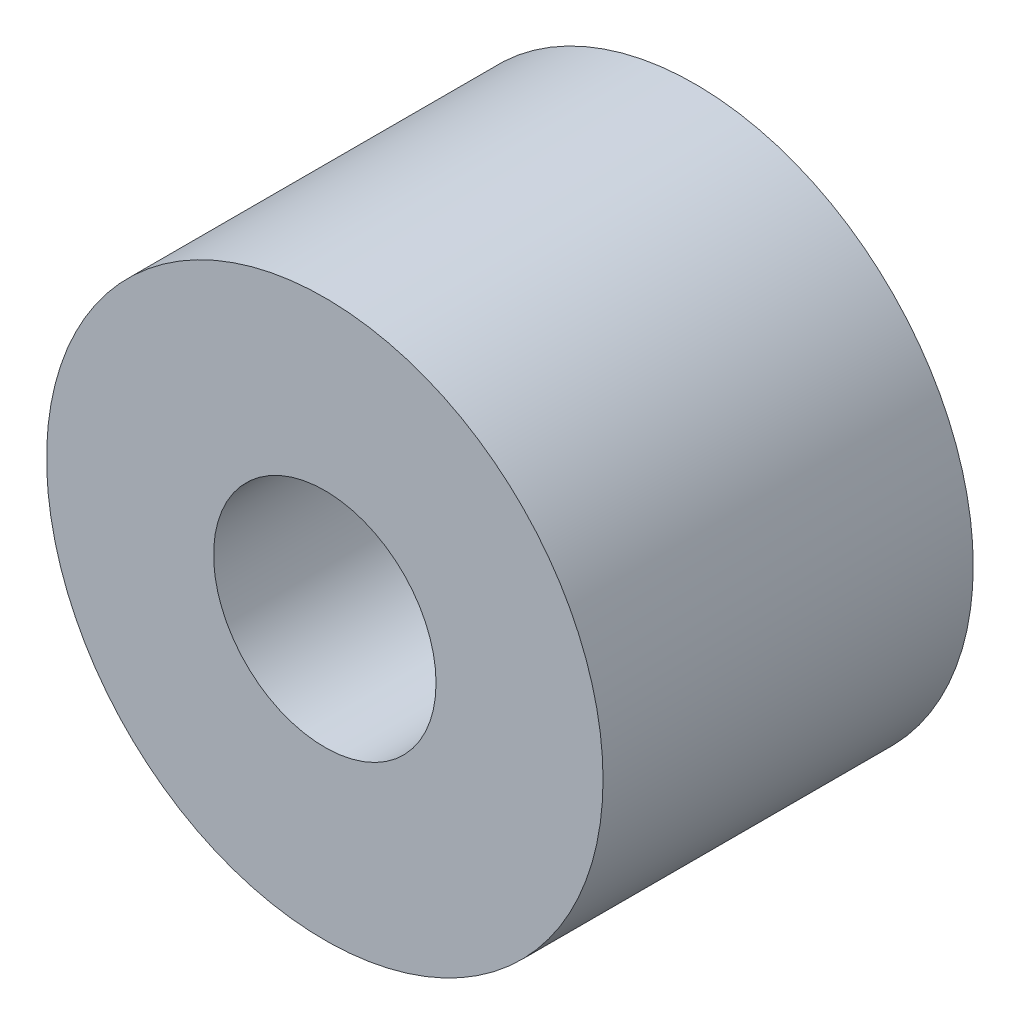
SolidWorks part; units mm, degrees
ref_plane "Płaszczyzna przednia" through (0, 0, 0) normal (0, 0, 1) x (1, 0, 0)
ref_plane "Płaszczyzna górna" through (0, 0, 0) normal (0, 1, 0) x (1, 0, 0)
ref_plane "Płaszczyzna prawa" through (0, 0, 0) normal (1, 0, 0) x (0, 0, -1)
sketch "Szkic2" plane through (0, 0, 0) normal (0, 0, 1) x (1, 0, 0)
  circle A0 centre (0, 0) radius 381
  circle A1 centre (0, 0) radius 953
  dimension "D1" = 762
  dimension "D2" = 1906
extrude "Dodanie-wyciągnięcie2" add sketch "Szkic2" along normal blind 1268
ref_axis "Oś3" through (0, 0, 1268) along (0, 0, -1)
